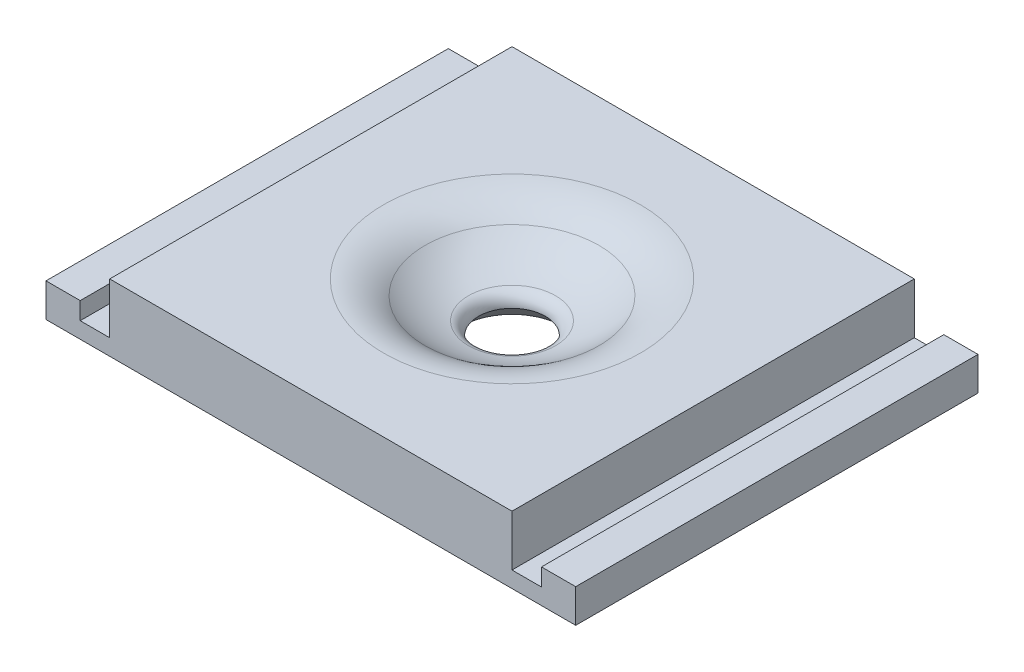
SolidWorks part; units mm, degrees
ref_plane "Front Plane" through (0, 0, 0) normal (0, 0, 1) x (1, 0, 0)
ref_plane "Top Plane" through (0, 0, 0) normal (0, 1, 0) x (1, 0, 0)
ref_plane "Right Plane" through (0, 0, 0) normal (1, 0, 0) x (0, 0, -1)
sketch "Sketch1" plane through (0, 0, 0) normal (0, 1, 0) x (1, 0, 0)
  line L1 (-15, -15) -> (15, -15)
  line L2 (-15, -15) -> (-15, 15)
  line L3 (-15, 15) -> (15, 15)
  line L4 (15, -15) -> (15, 15)
  line L5 (-15, -15) -> (15, 15) construction
  line L6 (-15, 15) -> (15, -15) construction
  point P0 (0, 0)
  dimension "D1" = 30
extrude "Main Body" add sketch "Sketch1" along normal blind 11
sketch "Sketch2" plane through (0, 0, 0) normal (0, -1, 0) x (1, 0, 0)
  line L0 (0, 15) -> (0, 8.6) construction
  line L1 (-15, 15) -> (15, 15) construction
  line L3 (-8.92, 7.2) -> (8.92, 7.2)
  line L4 (-8.92, 7.2) -> (-8.92, 10)
  line L5 (-8.92, 10) -> (8.92, 10)
  line L6 (8.92, 7.2) -> (8.92, 10)
  line L7 (-8.92, 7.2) -> (8.92, 10) construction
  line L8 (-8.92, 10) -> (8.92, 7.2) construction
  dimension "D1" = 6.4
  dimension "D2" = 2.8
  dimension "D3" = 17.84
extrude "Wire Hole" cut sketch "Sketch2" against normal blind 6 contours L4 L3 L6 L5
sketch "Sketch3" plane through (0, 0, 7.2) normal (0, 0, 1) x (1, 0, 0)
  line L0 (0, 0) -> (0, 4.2) construction
  line L2 (-10.25, 2.4) -> (10.25, 2.4)
  line L3 (-10.25, 2.4) -> (-10.25, 6)
  line L4 (-10.25, 6) -> (10.25, 6)
  line L5 (10.25, 2.4) -> (10.25, 6)
  line L6 (-10.25, 2.4) -> (10.25, 6) construction
  line L7 (-10.25, 6) -> (10.25, 2.4) construction
  dimension "D1" = 4.2
  dimension "D2" = 3.6
  dimension "D3" = 20.5
extrude "Board Cavity" cut sketch "Sketch3" against normal blind 17.2 and the other way blind 3
sketch "Sketch4" plane through (0, 6, 0) normal (0, -1, 0) x (1, 0, 0)
  line L0 (0, -10) -> (0, 0.05) construction
  line L1 (10.25, -10) -> (-10.25, -10) construction
  line L3 (-5, -4.95) -> (5, -4.95)
  line L4 (-5, -4.95) -> (-5, 5.05)
  line L5 (-5, 5.05) -> (5, 5.05)
  line L6 (5, -4.95) -> (5, 5.05)
  line L7 (-5, -4.95) -> (5, 5.05) construction
  line L8 (-5, 5.05) -> (5, -4.95) construction
  dimension "D1" = 10.05
  dimension "D2" = 10
extrude "Light Box" cut sketch "Sketch4" against normal blind 2
sketch "Sketch5" plane through (0, 8, 0) normal (0, -1, 0) x (1, 0, 0)
  line L0 (0, -4.95) -> (0, 0.05) construction
  line L1 (-5, -4.95) -> (5, -4.95) construction
  circle A0 centre (0, 0) radius 2.5
  dimension "D2" = 5
  dimension "D1" = 5
extrude "Cut-Extrude4" cut sketch "Sketch5" against normal blind 5
sketch "Sketch7" plane through (0, 0, -10) normal (0, 0, 1) x (1, 0, 0)
  line L0 (10.25, 2.4) -> (10.25, 6) construction
  line L5 (-10.25, 2.4) -> (10.25, 2.4)
  line L6 (-10.25, 2.4) -> (-10.25, 6)
  line L7 (-10.25, 6) -> (10.25, 6)
  line L8 (10.25, 2.4) -> (10.25, 6)
extrude "Cut-Extrude5" cut sketch "Sketch7" against normal blind 1
sketch "Sketch8" plane through (0, 0, -15) normal (0, 0, -1) x (-1, 0, 0)
  line L0 (-15, 5.5) -> (-15, 3.8)
  line L1 (-15, 11) -> (-15, 0) construction
  line L2 (-15, 3.8) -> (-17.2, 3.8)
  line L3 (-17.2, 3.8) -> (-17.2, 2.5)
  line L4 (-17.2, 2.5) -> (-19.75, 2.5)
  line L5 (-15, 5.5) -> (-15, 7.2)
  line L6 (-15, 7.2) -> (-17.2, 7.2)
  line L7 (-17.2, 7.2) -> (-17.2, 8.5)
  line L8 (-17.2, 8.5) -> (-19.75, 8.5)
  line L9 (-19.75, 8.5) -> (-19.75, 2.5)
  dimension "D1" = 1.7
  dimension "D2" = 2.2
  dimension "D3" = 1.3
  dimension "D4" = 2.55
  dimension "D5" = 1.7
  dimension "D6" = 2.2
  dimension "D7" = 1.3
  dimension "D8" = 2.55
extrude "Boss-Extrude1" add sketch "Sketch8" against normal blind 30
mirror "Mirror1" about plane through (0, 0, 0) normal (1, 0, 0) of "Boss-Extrude1"
sketch "Sketch9" plane through (0, 0, 0) normal (0, 0, 1) x (1, 0, 0)
  line L0 (5, 8) -> (-5, 8) construction
  line L1 (-2.5, 8) -> (2.5, 8) construction
  line L2 (-0.715, 25.9894) -> (-0.715, 8)
  line L3 (-1.3, 8) -> (-0.715, 8)
  arc A0 (-0.715, 25.9894) -> (-1.3, 8) centre (-0.91, 16.9915) ccw
  dimension "D1" = 9
sketch "Sketch10" plane through (0, 0, 0) normal (0, 0, 1) x (1, 0, 0)
  line L0 (0, 0) -> (0, -5) construction
  dimension "D1" = 5
revolve "Cut-Revolve6" cut sketch "Sketch9" angle 360 about L0
sketch "Sketch11" plane through (0, 8, 0) normal (0, -1, 0) x (1, 0, 0)
  line L1 (-5, 5.05) -> (5, 5.05)
  line L2 (-5, 5.05) -> (-5, -4.95)
  line L3 (-5, -4.95) -> (5, -4.95)
  line L4 (5, 5.05) -> (5, -4.95)
  circle A0 centre (0, 0) radius 2.5
extrude "Boss-Extrude2" add sketch "Sketch11" along normal blind 2
sketch "Sketch12" plane through (0, 0, -15) normal (0, 0, -1) x (-1, 0, 0)
  line L1 (-22.9498, 0) -> (21.6145, 0)
  line L2 (-22.9498, 0) -> (-22.9498, 6)
  line L3 (-22.9498, 6) -> (21.6145, 6)
  line L4 (21.6145, 0) -> (21.6145, 6)
  dimension "D1" = 6
extrude "Cut-Extrude6" cut sketch "Sketch12" against normal blind 40
fillet "Fillet1" radius 5 1 edges at (0, 11, -7.6258)
fillet "Fillet2" radius 1 1 edges at (0, 8.1331, 2.5)
sketch "Sketch13" plane through (0, 0, 0) normal (0, 0, 1) x (1, 0, 0)
  line L0 (-2.5, 7.3328) -> (-3.8328, 6)
  line L1 (-2.5, 7.3328) -> (2.5, 7.3328) construction
  line L2 (-19.75, 6) -> (19.75, 6) construction
  line L3 (-3.8328, 6) -> (0, 6)
  line L4 (-2.5, 6) -> (2.5, 6) construction
  line L5 (0, 6) -> (0, 7.3328)
  line L6 (0, 7.3328) -> (-2.5, 7.3328)
revolve "Cut-Revolve7" cut sketch "Sketch13" angle 360 about L0
